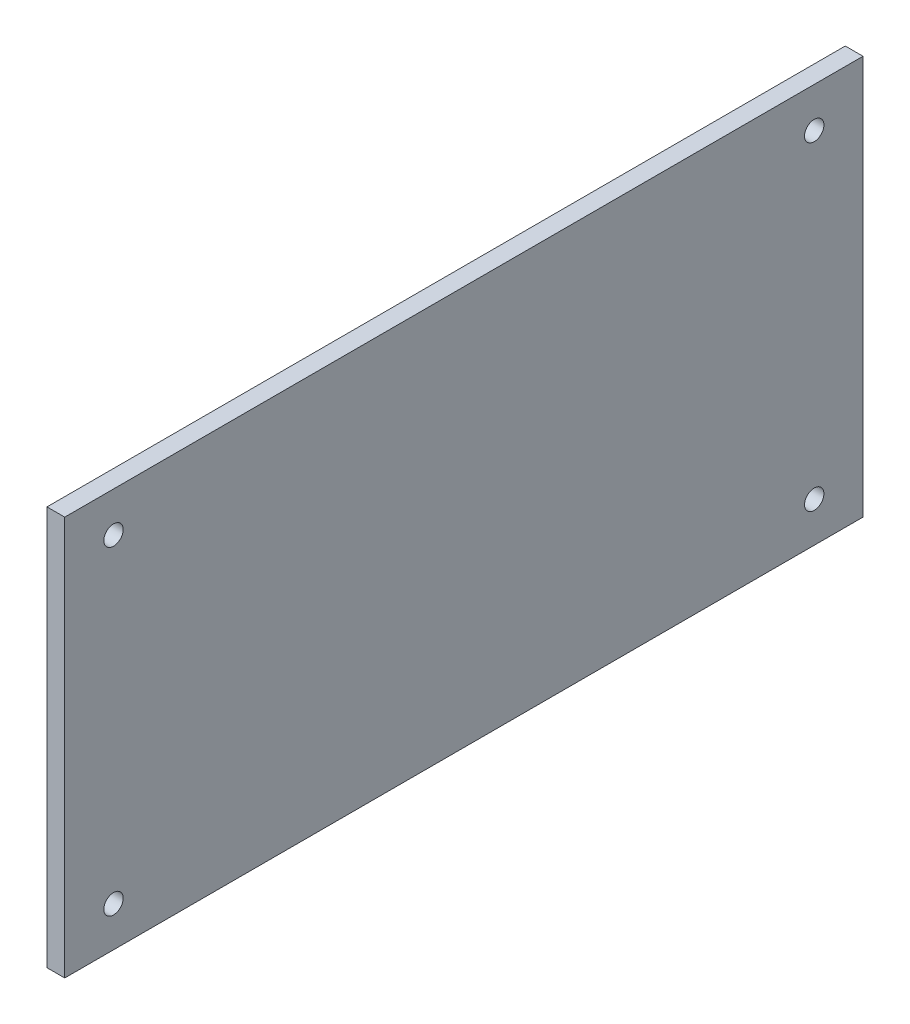
SolidWorks part; units mm, degrees
material "PCB (FR-4)"
ref_plane "Front Plane" through (0, 0, 0) normal (0, 0, 1) x (1, 0, 0)
ref_plane "Top Plane" through (0, 0, 0) normal (0, 1, 0) x (1, 0, 0)
ref_plane "Right Plane" through (0, 0, 0) normal (1, 0, 0) x (0, 0, -1)
sketch "Sketch1" plane through (0, 0, 0) normal (1, 0, 0) x (0, 0, -1)
  line L1 (-45, -22.5) -> (45, -22.5)
  line L2 (-45, -22.5) -> (-45, 22.5)
  line L3 (-45, 22.5) -> (45, 22.5)
  line L4 (45, -22.5) -> (45, 22.5)
  line L5 (-45, -22.5) -> (45, 22.5) construction
  line L6 (-45, 22.5) -> (45, -22.5) construction
  point P0 (0, 0)
  dimension "D1" = 45
  dimension "D2" = 90
extrude "Boss-Extrude1" add sketch "Sketch1" along normal blind 2
sketch "Sketch2" plane through (2, 0, 0) normal (1, 0, 0) x (0, 0, -1)
  line L0 (0, 0) -> (-39.5, 0) construction
  line L1 (-39.5, 0) -> (-39.5, -18) construction
  circle A0 centre (-39.5, -18) radius 1.0922
  circle A1 centre (39.5, -18) radius 1.0922
  circle A2 centre (39.5, 18) radius 1.0922
  circle A3 centre (-39.5, 18) radius 1.0922
  dimension "D3" = 2.1844
  dimension "D1" = 39.5
  dimension "D2" = 18
  dimension "D6" = 79
  dimension "D7" = 36
  dimension "D5" = 2
  dimension "D4" = 2
extrude "Cut-Extrude1" cut sketch "Sketch2" against normal blind 10
